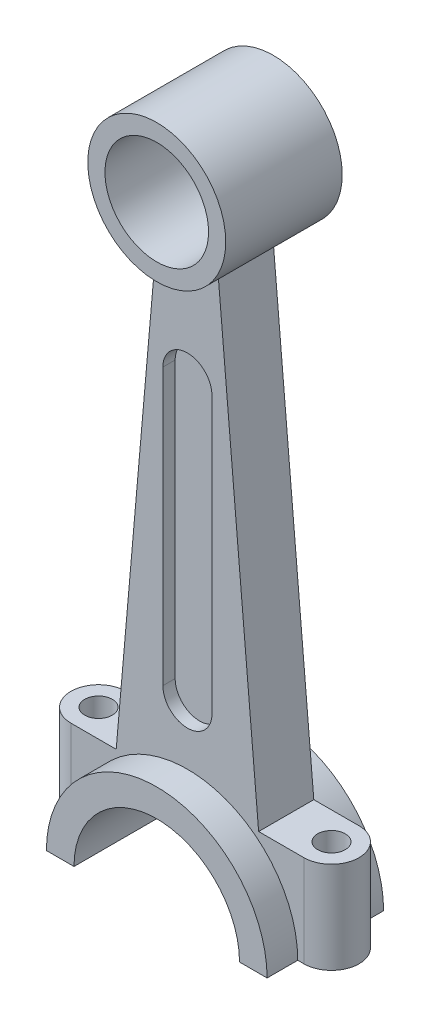
SolidWorks part; units mm, degrees
ref_plane "Front Plane" through (0, 0, 0) normal (0, 0, 1) x (1, 0, 0)
ref_plane "Top Plane" through (0, 0, 0) normal (0, 1, 0) x (1, 0, 0)
ref_plane "Right Plane" through (0, 0, 0) normal (1, 0, 0) x (0, 0, -1)
sketch "Sketch2" plane through (0, 0, 0) normal (0, 0, 1) x (1, 0, 0)
  line L0 (0, 0) -> (0, -201.2) construction
  line L1 (-10, -20.1556) -> (-23.4696, -173.902)
  line L2 (10, -20.1556) -> (23.4696, -173.902)
  circle A0 centre (0, 0) radius 22.5
  circle A1 centre (0, 0) radius 16.9
  circle A2 centre (0, -201.2) radius 27
  circle A3 centre (0, -201.2) radius 36
  point P9 (0, 0)
  dimension "D1" = 45
  dimension "D2" = 33.8
  dimension "D3" = 54
  dimension "D4" = 72
  dimension "D5" = 201.2
  dimension "D6" = 20
extrude "Boss-Extrude1" add sketch "Sketch2" along normal mid plane 38 contours A1 A0 | A3 A2 region at (-11.5231, 18.5805, 0) region at (0, -166.2182, 0)
extrude "Boss-Extrude2" add sketch "Sketch2<5>" along normal mid plane 18 contours L0 A0 L1 A3 | A0 L0 A3 L2 region at (8.8438, -104.2582, 0) region at (-8.8438, -104.2582, 0)
sketch "Sketch2<5>" plane through (0, 0, 0) normal (0, 0, 1) x (1, 0, 0) same geometry as "Sketch2"
sketch "Sketch3" plane through (0, 0, 9) normal (0, 0, 1) x (1, 0, 0)
  line L0 (0, 0) -> (0, -201.2) construction
  line L1 (0, -55.6) -> (0, -145.6) construction
  line L2 (8, -55.6) -> (8, -145.6)
  line L3 (-8, -55.6) -> (-8, -145.6)
  arc A0 (8, -55.6) -> (-8, -55.6) centre (0, -55.6) ccw
  arc A1 (-8, -145.6) -> (8, -145.6) centre (0, -145.6) ccw
  point P6 (0, -100.6)
  point P11 (0, -100.6)
  dimension "D1" = 8
  dimension "D2" = 90
extrude "Cut-Extrude1" cut sketch "Sketch3" against normal blind 4
mirror "Mirror1" about plane through (0, 0, 0) normal (0, 0, 1) of "Cut-Extrude1"
sketch "Sketch4" plane through (0, 0, 19) normal (0, 0, 1) x (1, 0, 0)
  line L0 (0, -201.2) -> (-54.7054, -201.2)
  line L1 (0, -201.2) -> (50.5446, -201.2)
  line L2 (50.5446, -201.2) -> (37.8617, -255.1914)
  line L3 (37.8617, -255.1914) -> (-51.5506, -248.9766)
  line L4 (-51.5506, -248.9766) -> (-54.7054, -201.2)
extrude "Cut-Extrude2" cut sketch "Sketch4" against normal blind 99
ref_plane "Plane1" through (0, -171.2, 0) normal (0, -1, 0) x (-1, 0, 0)
sketch "Sketch5" plane through (0, -171.2, 0) normal (0, -1, 0) x (-1, 0, 0)
  line L0 (38, 0) -> (-38, 0) construction
  line L1 (38, -9) -> (-38, -9)
  line L2 (38, 9) -> (-38, 9)
  arc A0 (38, -9) -> (38, 9) centre (38, 0) ccw
  arc A1 (-38, 9) -> (-38, -9) centre (-38, 0) ccw
  point P2 (0, 0)
  dimension "D2" = 9
  dimension "D1" = 76
extrude "Boss-Extrude3" add sketch "Sketch5" along normal up to surface (30 mm away) up to face at (-31.5, -201.2, 0)
sketch "Sketch6" plane through (0, 0, 9) normal (0, 0, 1) x (1, 0, 0)
  circle A0 centre (0, -201.2) radius 27
extrude "Cut-Extrude3" cut sketch "Sketch6" against normal blind 99
sketch "Sketch7" plane through (0, -171.2, 0) normal (0, 1, 0) x (1, 0, 0)
  circle A0 centre (38, 0) radius 4.5
  dimension "D1" = 9
extrude "Cut-Extrude4" cut sketch "Sketch7" against normal blind 99
mirror "Mirror2" about plane through (0, 0, 0) normal (1, 0, 0) of "Cut-Extrude4"
